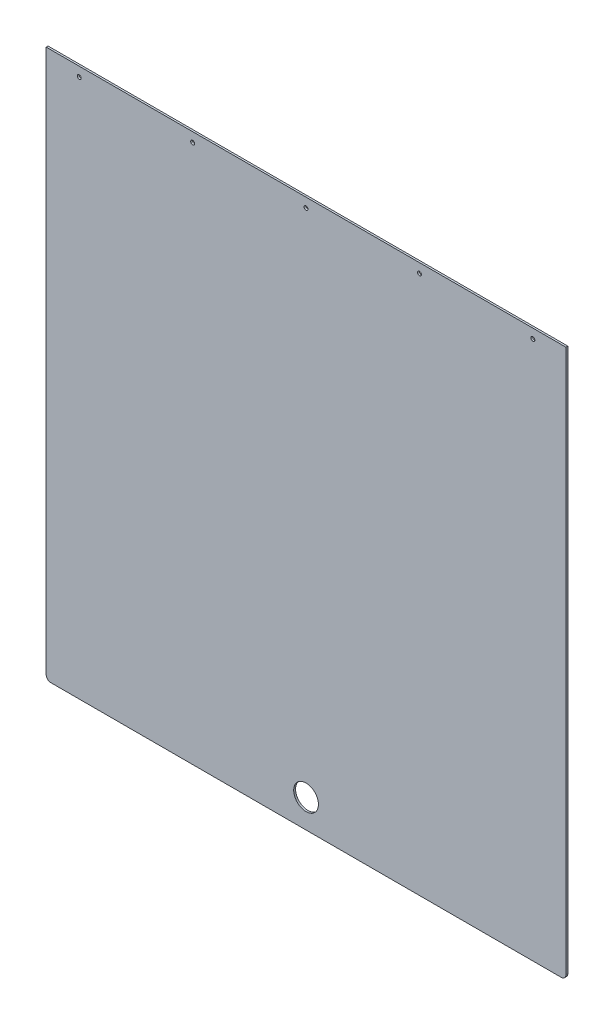
SolidWorks part; units mm, degrees
ref_plane "Płaszczyzna przednia" through (0, 0, 0) normal (0, 0, 1) x (1, 0, 0)
ref_plane "Płaszczyzna górna" through (0, 0, 0) normal (0, 1, 0) x (1, 0, 0)
ref_plane "Płaszczyzna prawa" through (0, 0, 0) normal (1, 0, 0) x (0, 0, -1)
sketch "Szkic1" plane through (0, 0, 0) normal (0, 0, 1) x (1, 0, 0)
  line L1 (-275, -290) -> (275, -290)
  line L2 (-275, -290) -> (-275, 290)
  line L3 (-275, 290) -> (275, 290)
  line L4 (275, -290) -> (275, 290)
  line L5 (-275, -290) -> (275, 290) construction
  line L6 (-275, 290) -> (275, -290) construction
  point P0 (0, 0)
  dimension "D1" = 580
  dimension "D2" = 550
base flange "Odgięcie bazowe1" sketch "Szkic1" thickness 2 reverse thickness direction no parameters "D1"=0.7366
fillet "Zaokrąglenie1" radius 5 2 edges at (-275, -290, -1) (275, -290, -1)
sketch "Szkic3" plane through (0, 0, 0) normal (0, 0, 1) x (1, 0, 0)
  line L0 (0, 290) -> (0, 0) construction
  line L1 (275, 290) -> (-275, 290) construction
  circle A0 centre (0, 280) radius 2.1
  circle A1 centre (120, 280) radius 2.1
  circle A2 centre (240, 280) radius 2.1
  circle A3 centre (-240, 280) radius 2.1
  circle A4 centre (-120, 280) radius 2.1
  dimension "D1" = 10
  dimension "D2" = 4.2
  dimension "D3" = 3
extrude "Wytnij-wyciągnięcie2" cut sketch "Szkic3" against normal up to next normal cut yes
sketch "Szkic4" plane through (0, 0, -2) normal (0, 0, -1) x (-1, 0, 0)
  line L0 (0, -290) -> (0, 290) construction
  line L1 (-275, 290) -> (275, 290) construction
  line L2 (270, -290) -> (-270, -290) construction
  circle A0 centre (0, -260) radius 13.1
  point P5 (0, 290)
  point P9 (0, -290)
  dimension "D1" = 26.2
  dimension "D2" = 30
extrude "Wytnij-wyciągnięcie3" cut sketch "Szkic4" against normal up to next normal cut yes
sketch "Linie zgięcia1" [suppressed] plane through (0, 0, 0) normal (0, 1, 0) x (1, 0, 0)
sketch "Ramka-graniczna1" [suppressed] plane through (0, 0, 0) normal (0, 1, 0) x (1, 0, 0)
sheet metal parameters "Arkusz blachy1" thickness 2 parameters "D1"=0.7366
flat pattern "Rozłożony model1" [suppressed]
sketch "Linie zgięcia2" plane through (0, 0, 0) normal (0, 1, 0) x (1, 0, 0)
sketch3d "Ramka-graniczna2" [suppressed]
  line L0 (275, -290, 0) -> (275, 290, 0) construction
  line L1 (-275, -290, 0) -> (-275, 290, 0) construction
  line L2 (275, -290, 0) -> (-275, -290, 0) construction
  line L3 (275, 290, 0) -> (-275, 290, 0) construction
sheet metal parameters "Arkusz blachy3" thickness 2 parameters "D1"=0.7366
flat pattern "Rozłożony model1"
sketch "Linie zgięcia2" plane through (0, 0, 0) normal (0, 1, 0) x (1, 0, 0)
sketch3d "Ramka-graniczna2" [suppressed]
  line L0 (275, -290, 0) -> (275, 290, 0) construction
  line L1 (-275, -290, 0) -> (-275, 290, 0) construction
  line L2 (275, -290, 0) -> (-275, -290, 0) construction
  line L3 (275, 290, 0) -> (-275, 290, 0) construction
sheet metal parameters "Arkusz blachy4" thickness 2 parameters "D1"=0.7366
flat pattern "Rozłożony model1"
sketch "Linie zgięcia2" plane through (0, 0, 0) normal (0, 1, 0) x (1, 0, 0)
sketch3d "Ramka-graniczna2" [suppressed]
  line L0 (275, -290, 0) -> (275, 290, 0) construction
  line L1 (-275, -290, 0) -> (-275, 290, 0) construction
  line L2 (275, -290, 0) -> (-275, -290, 0) construction
  line L3 (275, 290, 0) -> (-275, 290, 0) construction
